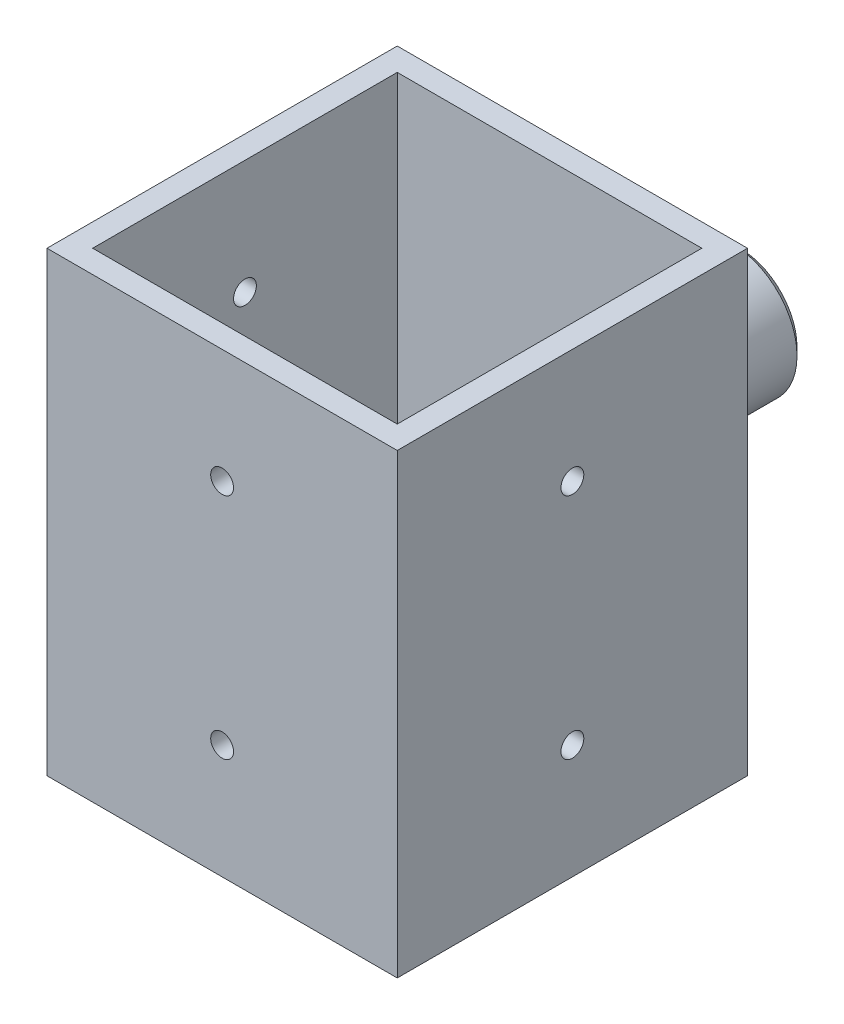
SolidWorks part; units mm, degrees
material "PA Type 6"
ref_plane "Front Plane" through (0, 0, 0) normal (0, 0, 1) x (1, 0, 0)
ref_plane "Top Plane" through (0, 0, 0) normal (0, 1, 0) x (1, 0, 0)
ref_plane "Right Plane" through (0, 0, 0) normal (1, 0, 0) x (0, 0, -1)
sketch "Esquisse1" plane through (0, 0, 0) normal (0, 0, 1) x (1, 0, 0)
  circle A0 centre (0, 0) radius 8.5
  dimension "D1" = 17
extrude "Boss.-Extru.1" add sketch "Esquisse1" along normal blind 10
sketch "Esquisse2" plane through (0, 0, 10) normal (0, 0, 1) x (1, 0, 0)
  circle A0 centre (0, 0) radius 11
  dimension "D1" = 22
extrude "Boss.-Extru.2" add sketch "Esquisse2" along normal blind 12
ref_axis "Axe1" through (0, 0, 10) along (0, 0, -1)
sketch "Esquisse3" plane through (0, 0, 0) normal (0, 0, -1) x (-1, 0, 0)
  line L0 (0, 4.9) -> (0, -0.1563) construction
  circle A0 centre (0, 4.9) radius 2
  circle A1 centre (0, 4.9) radius 3.6 construction
  circle A2 centre (0, 0) radius 8.5 construction
  circle A3 centre (4.2435, -2.45) radius 2
  circle A4 centre (-4.2435, -2.45) radius 2
  point P13 (0, 0)
  dimension "D1" = 7.2
  dimension "D2" = 4
  dimension "D3" = 3
extrude "Enlèv. mat.-Extru.1" cut sketch "Esquisse3" against normal blind 8
chamfer "Chanfrein1" distance 1 angle 45 1 edges at (8.5, 0, 0)
sketch "Esquisse4" plane through (0, 0, 0) normal (0, 1, 0) x (1, 0, 0)
  line L1 (-23, -22) -> (23, -22)
  line L2 (-23, -22) -> (-23, -68)
  line L3 (-23, -68) -> (23, -68)
  line L4 (23, -22) -> (23, -68)
  line L5 (-20, -25) -> (20, -25)
  line L6 (-20, -25) -> (-20, -65)
  line L7 (-20, -65) -> (20, -65)
  line L8 (20, -25) -> (20, -65)
  dimension "D1" = 46
  dimension "D2" = 0
  dimension "D3" = 23
  dimension "D4" = 40
  dimension "D5" = 3
  dimension "D6" = 3
extrude "Boss.-Extru.3" add sketch "Esquisse4" along normal blind 30 and the other way blind 30
sketch "Esquisse5" plane through (23, 0, 0) normal (1, 0, 0) x (0, 0, -1)
  line L0 (-45, 15) -> (-45, -15) construction
  circle A0 centre (-45, 15) radius 1.5
  circle A1 centre (-45, -15) radius 1.5
  dimension "D1" = 3
  dimension "D2" = 30
  dimension "D3" = 20
  dimension "D4" = 15
extrude "Enlèv. mat.-Extru.2" cut sketch "Esquisse5" against normal through all both and the other way through all
sketch "Esquisse6" plane through (0, 0, 68) normal (0, 0, 1) x (1, 0, 0)
  line L0 (0, 15) -> (0, -15) construction
  circle A0 centre (0, 15) radius 1.5
  circle A1 centre (0, -15) radius 1.5
  dimension "D1" = 3
  dimension "D2" = 30
extrude "Enlèv. mat.-Extru.3" cut sketch "Esquisse6" against normal blind 10
fillet "Congé1" radius 10 1 edges at (11, 0, 22)
